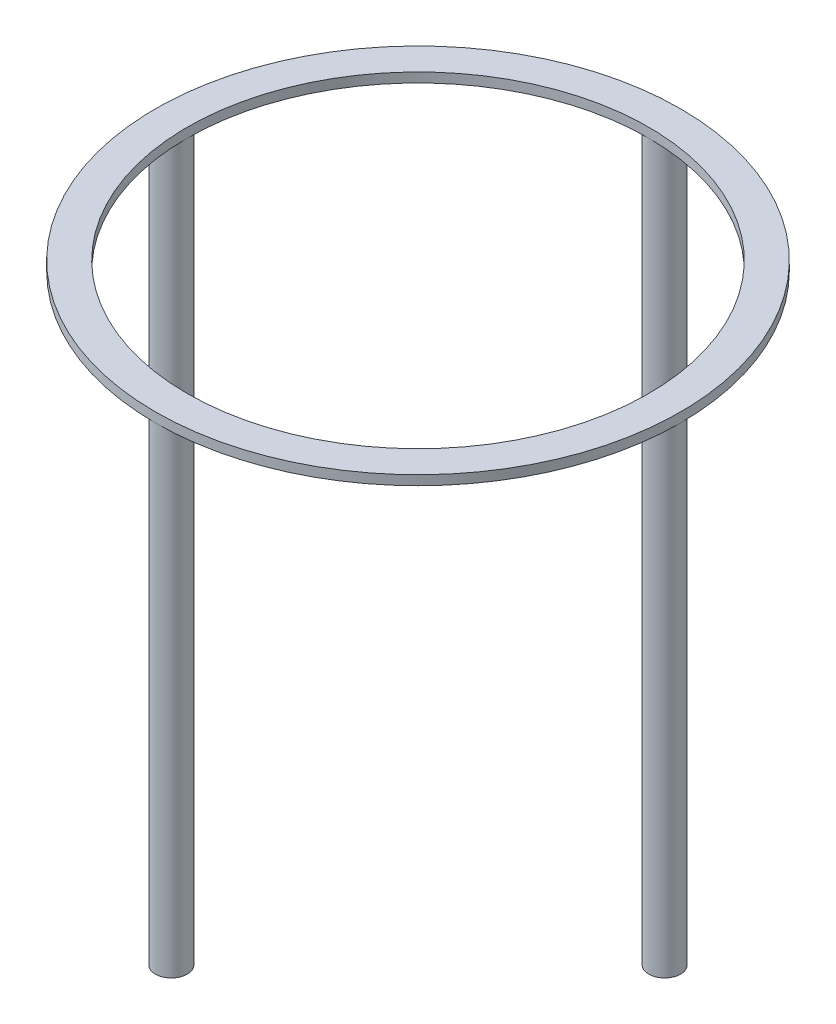
SolidWorks part; units mm, degrees
ref_plane "Front Plane" through (0, 0, 0) normal (0, 0, 1) x (1, 0, 0)
ref_plane "Top Plane" through (0, 0, 0) normal (0, 1, 0) x (1, 0, 0)
ref_plane "Right Plane" through (0, 0, 0) normal (1, 0, 0) x (0, 0, -1)
sketch "Sketch1" plane through (0, 0, 0) normal (0, 1, 0) x (1, 0, 0)
  circle A2 centre (0, 0) radius 72.5
  circle A3 centre (0, 0) radius 82.5
extrude "Boss-Extrude1" add sketch "Sketch1" along normal blind 3
sketch "Sketch2" plane through (0, 0, 0) normal (0, 1, 0) x (1, 0, 0)
  circle A0 centre (-77.5, 0) radius 5
  circle A1 centre (0, -77.5) radius 5
  circle A2 centre (77.5, 0) radius 5
  circle A3 centre (0, 77.5) radius 5
  dimension "D5" = 10
  dimension "D6" = 10
  dimension "D7" = 10
  dimension "D8" = 10
extrude "Boss-Extrude2" add sketch "Sketch2" against normal blind 150
ref_axis "Axis1" through (0, 3, 0) along (0, -1, 0)
